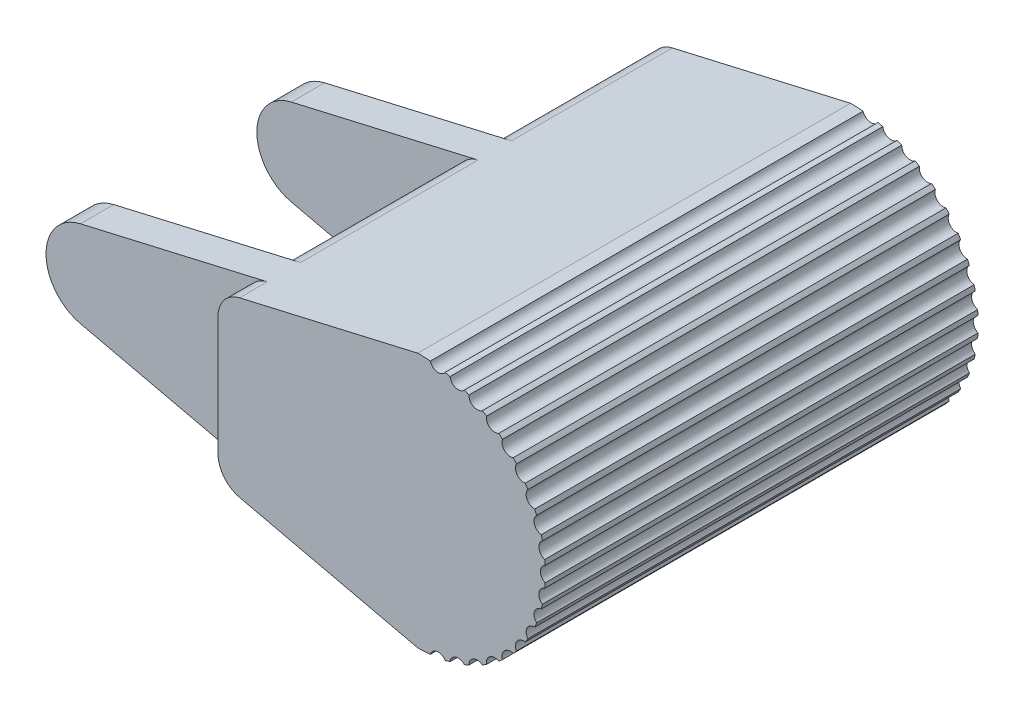
SolidWorks part; units mm, degrees
material "Borracha de silicone"
ref_plane "Plano frontal" through (0, 0, 0) normal (0, 0, 1) x (1, 0, 0)
ref_plane "Plano superior" through (0, 0, 0) normal (0, 1, 0) x (1, 0, 0)
ref_plane "Plano direito" through (0, 0, 0) normal (1, 0, 0) x (0, 0, -1)
sketch "Esboço1" plane through (0, 0, 0) normal (0, 0, 1) x (1, 0, 0)
  line L0 (-0.9006, 3.8973) -> (32, 11.5)
  line L1 (-0.9006, -3.8973) -> (32, -11.5)
  line L3 (32, 11.5) -> (32, -11.5) construction
  line L4 (0, 0) -> (43.5, 0) construction
  line L5 (14, 5.3524) -> (14, -5.3524)
  arc A0 (-0.9006, 3.8973) -> (-0.9006, -3.8973) centre (0, 0) ccw
  arc A1 (32, -11.5) -> (32, 11.5) centre (32, 0) ccw
  arc A2 (15.9371, 7.7882) -> (14, 5.3524) centre (16.5, 5.3524) ccw
  arc A3 (15.9371, -7.7882) -> (14, -5.3524) centre (16.5, -5.3524) cw
  point P15 (14, 0)
  dimension "D1" = 8
  dimension "D5" = 18
  dimension "D6" = 2.5
  dimension "D2" = 32
  dimension "D3" = 23
extrude "Ressalto-extrusão1" add sketch "Esboço1" along normal mid plane 39 contours A3 L1 A1 L0 A2 L5 region at (28.7239, 0, 0)
extrude "Ressalto-extrusão2" add sketch "Esboço1<3>" against normal blind 3 from offset 17 contours L1 A3 L5 A2 L0 A0 region at (6.4549, 0, 0)
sketch "Esboço1<3>" plane through (0, 0, 0) normal (0, 0, 1) x (1, 0, 0) same geometry as "Esboço1"
extrude "Ressalto-extrusão3" add sketch "Esboço1<4>" along normal blind 3 from offset 5 contours L1 A3 L5 A2 L0 A0 region at (6.4549, 0, 0) offset against normal yes
sketch "Esboço1<4>" plane through (0, 0, 0) normal (0, 0, 1) x (1, 0, 0) same geometry as "Esboço1"
sketch "Esboço2" plane through (14, 0, 0) normal (-1, 0, 0) x (0, 0, 1)
  line L0 (14, -5.3524) -> (14, -7.7882) construction
  line L1 (13, 5.0524) -> (-1, 5.0524)
  line L2 (13, 5.0524) -> (13, -4.9476)
  line L3 (13, -4.9476) -> (-1, -4.9476)
  line L4 (-1, 5.0524) -> (-1, -4.9476)
  line L5 (13, 5.0524) -> (-1, -4.9476) construction
  line L6 (13, -4.9476) -> (-1, 5.0524) construction
  line L7 (-2, -3.8973) -> (-2, 3.8973) construction
  line L8 (14, 5.3524) -> (-2, 5.3524) construction
  point P0 (6, 0.0524)
  dimension "D1" = 1
  dimension "D2" = 1
  dimension "D3" = 10
  dimension "D4" = 0.3
extrude "Corte-extrusão1" cut sketch "Esboço2" against normal blind 13
sketch "Esboço4" plane through (0, 0, 0) normal (0, 0, 1) x (1, 0, 0)
  line L0 (0, 0) -> (48.9475, 0) construction
  circle A0 centre (43.8, 0) radius 0.75
  arc A2 (32, -11.5) -> (32, 11.5) centre (32, 0) ccw construction
  dimension "D1" = 1.5
  dimension "D2" = 11.8
extrude "Corte-extrusão2" cut sketch "Esboço4" against normal mid plane 103
pattern_circular "PadrãoCircular1" count 10 every 9 about axis through (32, 0, 19.5) along (0, 0, 1) of "Corte-extrusão2" other way count 10
